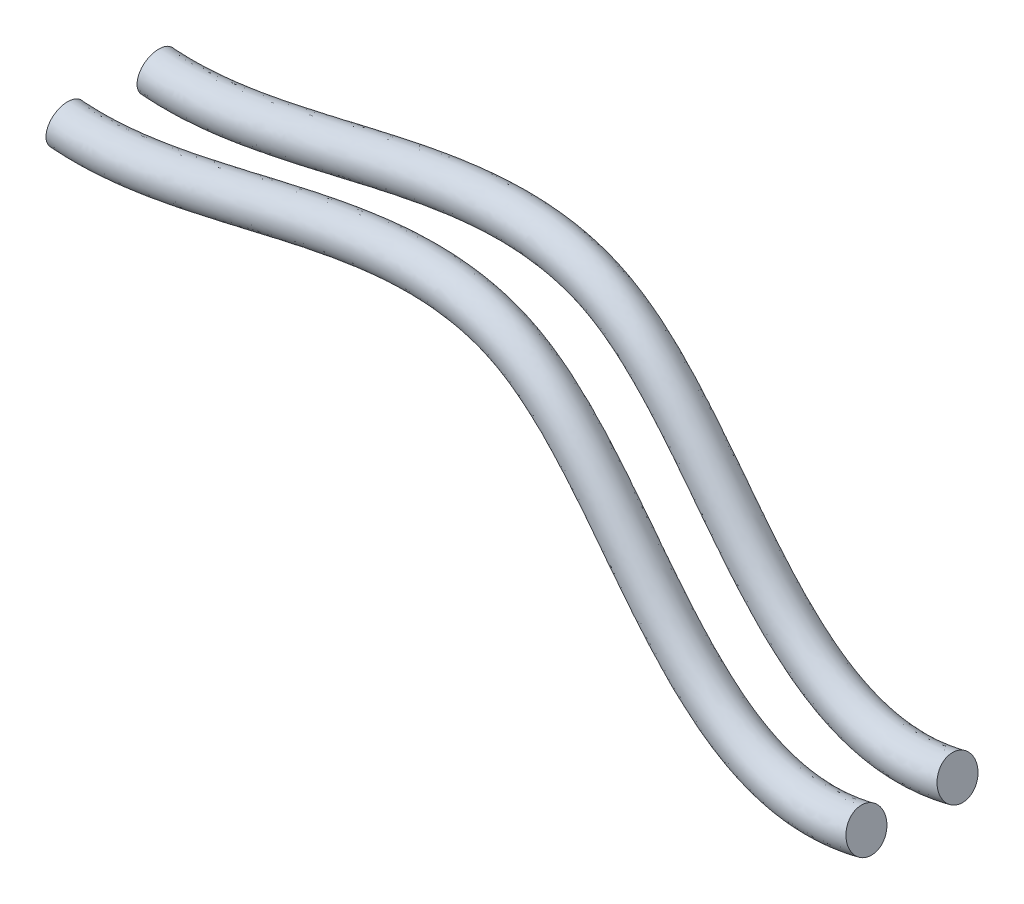
SolidWorks part; units mm, degrees
ref_plane "Спереди" through (0, 0, 0) normal (0, 0, 1) x (1, 0, 0)
ref_plane "Сверху" through (0, 0, 0) normal (0, 1, 0) x (1, 0, 0)
ref_plane "Справа" through (0, 0, 0) normal (1, 0, 0) x (0, 0, -1)
sketch "Эскиз1" plane through (0, 0, 0) normal (0, 0, 1) x (1, 0, 0)
  line L1 (-45.1219, -19.9026) -> (-35.1683, -18.9398)
  line L2 (-35.1683, -18.9398) -> (-10.2232, -17.2849)
  line L3 (-10.2232, -17.2849) -> (7.3741, -35.0426)
  line L4 (7.3741, -35.0426) -> (17.281, -36.4039)
  spline S0 degree 3 poles (-45.1219, -19.9026) (-34.409, -20.8102) (-4.9031, -4.1469) (3.3227, -40.0357) (17.281, -36.4039) knots 0 0 0 0 0.5 1 1 1 1
  point P1 (11.3194, 0)
  point P2 (9.0322, -26.382)
  point P10 (24.1045, 0)
  point P11 (27.3892, 0)
  point P12 (10.3975, 0)
  point P13 (39.4093, 0)
  point P14 (22.2224, 0)
  point P15 (-15.0091, -6.036)
  point P16 (0, 0)
  point P17 (20.5981, -28.3192)
  point P18 (17.281, -36.4039)
  point P19 (1.7749, -10.6777)
  point P20 (-45.1219, -19.9026)
  dimension "D1" = 10
  dimension "D2" = 25
  dimension "D3" = 25
  dimension "D4" = 10
ref_plane "Плоскость1" through (-45.1219, -19.9026, 0) normal (0.9964, -0.0844, 0) x (0, 0, -1)
sketch "Эскиз2" plane through (-45.1219, -19.9026, 0) normal (0.9964, -0.0844, 0) x (0, 0, -1)
  line L0 (0, 0) -> (-7.1661, 0) construction
  circle A0 centre (0, 0) radius 1.55
  circle A1 centre (-7.1, 0) radius 1.55
  dimension "D1" = 3.1
  dimension "D2" = 3.1
  dimension "D3" = 7.1
sweep "По траектории1" add profiles "Эскиз2" path "Эскиз1"
